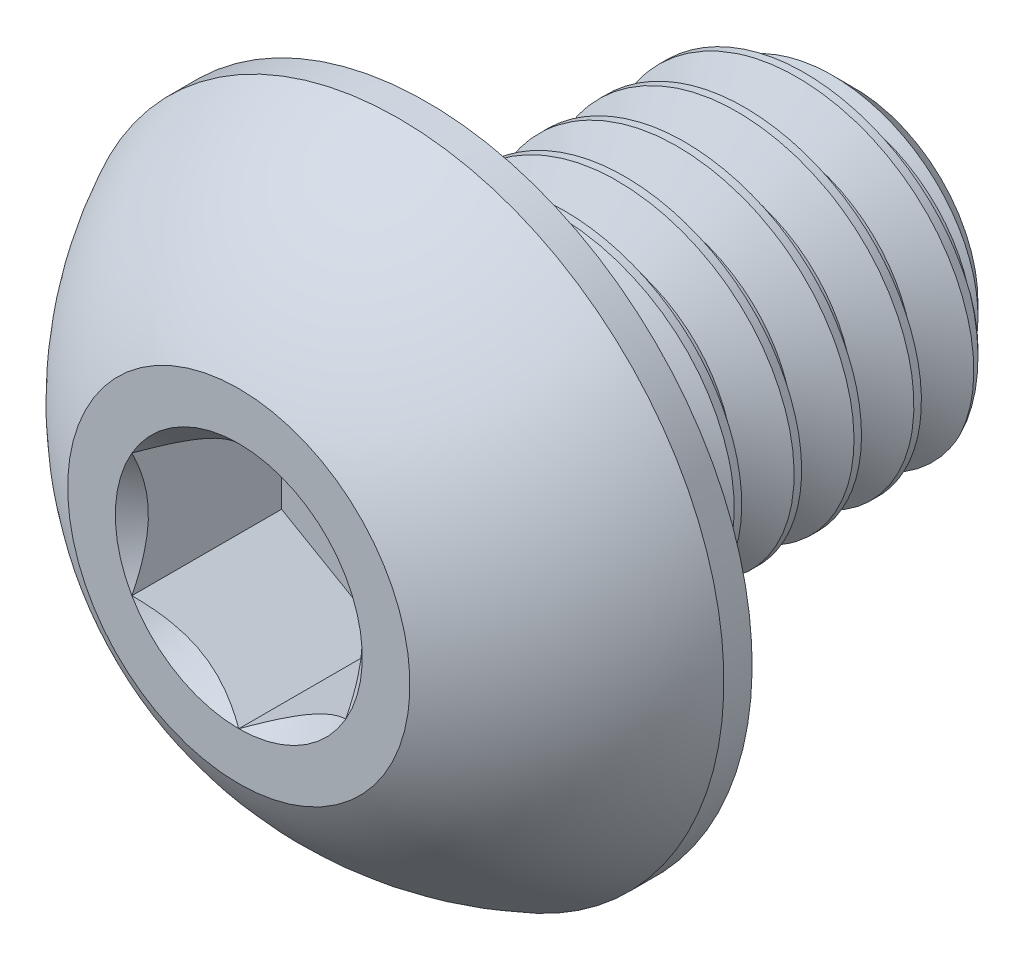
SolidWorks part; units mm, degrees
ref_plane "Front Plane" through (0, 0, 0) normal (0, 0, 1) x (1, 0, 0)
ref_plane "Top Plane" through (0, 0, 0) normal (0, 1, 0) x (1, 0, 0)
ref_plane "Right Plane" through (0, 0, 0) normal (1, 0, 0) x (0, 0, -1)
sketch "Sketch1" plane through (0, 0, 0) normal (1, 0, 0) x (0, 0, -1)
  line L0 (-3.6, 0) -> (3.6, 0) construction
  line L1 (-1.4, 3.8) -> (-1.4, -3.8) construction
  line L2 (3.6, 2) -> (3.6, -2) construction
  line L3 (3.5563, 2.0758) -> (3.9063, 1.4696) construction
  line L4 (3.9063, 1.4696) -> (4.2563, 2.0758) construction
  line L5 (4.2563, 2.0758) -> (3.5563, 2.0758) construction
  line L6 (3.6, 2) -> (4.2125, 2) construction
  line L7 (3.9063, 2.0758) -> (3.9063, 2) construction
  line L8 (3.9063, 2) -> (3.9063, 1.5453) construction
  line L9 (3.9063, 1.5453) -> (3.9063, 1.4696) construction
  line L10 (3.8625, 1.5453) -> (3.95, 1.5453)
  line L11 (3.5781, 2.0379) -> (4.2344, 2.0379)
  line L12 (3.95, 1.5453) -> (4.2344, 2.0379)
  line L13 (3.8625, 1.5453) -> (3.5781, 2.0379)
  line L14 (-3.6, 1.25) -> (-3.6, -1.25) construction
  line L15 (3.6, 2) -> (-1.4, 2) construction
  point P3 (-1.4, 0)
  point P6 (-1.85, 0)
  point P21 (3.9063, 2.0379)
  point P24 (-1.73, 3.8)
  point P25 (1.85, -2)
  point P26 (-3.6, 2)
  dimension "Head Height" = 2.2
  dimension "Length" = 5
  dimension "Head Dia" = 7.6
  dimension "Thread Dia" = 4
  dimension "Pitch" = 0.7
  dimension "Drive Size" = 2.5
  dimension "D1" = 1.75
  dimension "D3" = 0.33
  dimension "D4" = 1.75
sketch "Sketch2" plane through (0, 0, 0) normal (1, 0, 0) x (0, 0, -1)
  line L0 (-3.6, 0) -> (3.6, 0)
  line L1 (3.6, 0) -> (3.6, 1.44)
  line L2 (3.6, 2) -> (3.6, -2) construction
  line L3 (3.6, 1.44) -> (3.04, 2)
  line L4 (3.04, 2) -> (-1.4, 2)
  line L5 (-1.4, 3.8) -> (-1.4, -3.8) construction
  line L6 (-1.4, 2) -> (-1.4, 3.8)
  line L7 (-1.4, 3.8) -> (-1.73, 3.8)
  line L8 (3.6, 2) -> (4.2125, 2) construction
  line L9 (-3.6, 0) -> (-3.6, 2)
  arc A0 (-3.6, 2) -> (-1.73, 3.8) centre (0.1264, 0) cw
  dimension "D1" = 0.56
  dimension "D2" = 45
revolve "Revolve1" add sketch "Sketch2" angle 360 about L0
sketch "Sketch3" plane through (0, 0, 3.6) normal (0, 0, 1) x (1, 0, 0)
  line L1 (0, 1.4434) -> (-1.25, 0.7217)
  line L2 (-1.25, 0.7217) -> (-1.25, -0.7217)
  line L3 (-1.25, -0.7217) -> (0, -1.4434)
  line L4 (0, -1.4434) -> (1.25, -0.7217)
  line L5 (1.25, -0.7217) -> (1.25, 0.7217)
  line L6 (1.25, 0.7217) -> (0, 1.4434)
  circle A0 centre (0, 0) radius 1.25 construction
  dimension "D1" = 2.5
extrude "Cut-Extrude1" cut sketch "Sketch3" against normal up to vertex (1.75 mm away) up to point (0, 0, 1.85)
sketch "Sketch4" plane through (0, 0, 3.6) normal (0, 0, 1) x (1, 0, 0)
  circle A0 centre (0, 0) radius 1.4434
extrude "Cut-Extrude2" cut sketch "Sketch4" against normal blind 10 draft 45
split "Split1" bodies to split 106 resulting bodies 107 108 split by face at (0, -3.8, 1.4)
sketch "Sketch5" plane through (0, 0, -3.6) normal (0, 0, -1) x (-1, 0, 0)
  circle A0 centre (0, 0) radius 2 construction
  circle A1 centre (0, 0) radius 2
curve "Helix/Spiral1" pitch 0.7 height 5.7 radius 2 centre (0, 0, -3.6) axis (0, 0, 1) start towards (0, 1, 0)
sketch "Sketch6" plane through (0, 0, 0) normal (1, 0, 0) x (0, 0, -1)
  line L0 (3.8625, 1.5453) -> (3.95, 1.5453) construction
  line L1 (3.8625, 1.5453) -> (3.5781, 2.0379) construction
  line L2 (3.5781, 2.0379) -> (4.2344, 2.0379) construction
  line L3 (3.95, 1.5453) -> (4.2344, 2.0379) construction
  line L4 (3.8625, 1.5453) -> (3.95, 1.5453)
  line L5 (3.8625, 1.5453) -> (3.5781, 2.0379)
  line L6 (3.5781, 2.0379) -> (4.2344, 2.0379)
  line L7 (3.95, 1.5453) -> (4.2344, 2.0379)
sweep "Cut-Sweep1" cut profiles "Sketch6" path "Helix/Spiral1" align with end faces yes
sketch "Sketch7" plane through (0, 0, 1.4) normal (0, 0, -1) x (-1, 0, 0)
  circle A1 centre (0, 0) radius 2
  circle A2 centre (0, 0) radius 2
  dimension "D1" = 0
extrude "Boss-Extrude1" add sketch "Sketch7" along normal blind 10 draft 30
equation "\"D2@Sketch1\" = \"Pitch@Sketch1\" / 8"
equation "\"D1@Sketch1\"=\"Drive Size@Sketch1\"*.7"
equation "\"D3@Sketch1\"=\"Head Height@Sketch1\"*.15"
equation "\"D1@Sketch2\"=\"Pitch@Sketch1\"*.8"
equation "\"D1@Sketch3\"=\"Drive Size@Sketch1\""
equation "\"D4@Helix/Spiral1\"=\"Pitch@Sketch1\""
equation "\"D3@Helix/Spiral1\"=\"Length@Sketch1\"+\"Pitch@Sketch1\""
equation "\"D4@Sketch1\"=\"Pitch@Sketch1\"*2.5"
